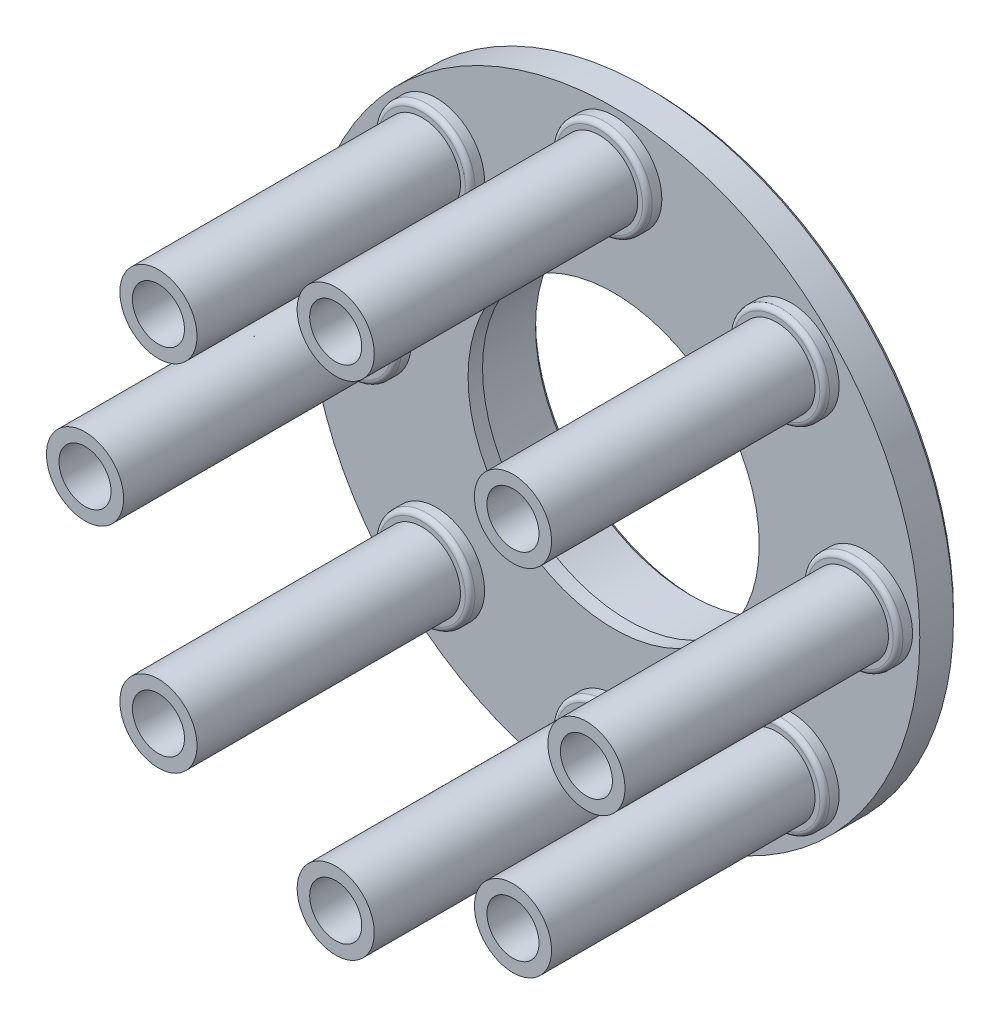
SolidWorks part; units mm, degrees
material "PLA"
ref_plane "Front Plane" through (0, 0, 0) normal (0, 0, 1) x (1, 0, 0)
ref_plane "Top Plane" through (0, 0, 0) normal (0, 1, 0) x (1, 0, 0)
ref_plane "Right Plane" through (0, 0, 0) normal (1, 0, 0) x (0, 0, -1)
sketch "Sketch1" plane through (0, 0, 0) normal (0, 0, 1) x (1, 0, 0)
  circle A0 centre (0, 0) radius 31.75
  circle A1 centre (0, 0) radius 26 construction
  circle A2 centre (0, 26) radius 2.7
  circle A3 centre (26, 0) radius 2.7
  circle A78 centre (0, -26) radius 2.7
  circle A79 centre (0, 26) radius 4.25 construction
  circle A80 centre (0, 0) radius 30.25 construction
  circle A87 centre (-26, 0) radius 2.7
  point P15 (0, 0)
  dimension "D2" = 52
  dimension "D3" = 5.4
  dimension "D5" = 8.5
  dimension "D1" = 1.5
  dimension "D4" = 4
extrude "Boss-Extrude1" add sketch "Sketch1" along normal blind 4
sketch "Sketch2" plane through (0, 0, 4) normal (0, 0, 1) x (1, 0, 0)
  circle A0 centre (0, 26) radius 4
  circle A2 centre (0, 26) radius 2.7 construction
  circle A5 centre (0, 26) radius 2.7
  point P15 (0, 0)
  dimension "D1" = 8
extrude "Boss-Extrude2" add sketch "Sketch2" along normal blind 28.8234
sketch "Sketch3" plane through (0, 0, 4) normal (0, 0, 1) x (1, 0, 0)
  arc A2 (5, 26) -> (5, 26) centre (0, 26) ccw
  circle A3 centre (0, 26) radius 5
  circle M5 centre (0, 26) radius 4
extrude "Boss-Extrude3" add sketch "Sketch3" along normal blind 1.5 contours A3 M5 region at (-4.8586, 26, 4)
sketch "Sketch4" plane through (0, 0, 4) normal (0, 0, 1) x (1, 0, 0)
  line L0 (0, 0) -> (-22.4506, 22.4506) construction
  line L1 (0, 0) -> (0, 26) construction
  circle A0 centre (0, 0) radius 31.75 construction
  circle A1 centre (0, 0) radius 31.75
  circle A2 centre (0, 26) radius 12 construction
  circle A6 centre (0, 0) radius 26 construction
  arc A8 (-13.189, 28.881) -> (-9.5294, 16.4375) centre (0, 26) ccw
  circle A9 centre (0, 0) radius 19
  circle A11 centre (0, 0) radius 14 construction
  arc A13 (-28.881, 13.189) -> (-16.4375, 9.5294) centre (-26, 0) cw
  circle A16 centre (0, 26) radius 13.5 construction
  circle A17 centre (0, 26) radius 5 construction
  point P15 (0, 0)
  point P25 (0, 0)
  dimension "D1" = 24
  dimension "D5" = 28
  dimension "D4" = 5
  dimension "D2" = 45
  dimension "D3" = 1.5
extrude "Boss-Extrude4" [suppressed] add sketch "Sketch4" along normal blind 28.8234 contours A1 A13 A9 A8
sketch "Sketch12" [suppressed] plane through (0, 0, 37.8382) normal (0, 0, 1) x (1, 0, 0)
  arc A0 (-11.2345, 15.816) -> (-15.816, 11.2345) centre (0, 0) ccw construction
  arc A1 (-11.2345, 15.816) -> (-15.816, 11.2345) centre (0, 0) ccw
  dimension "D1" = 6.4791
fillet "Fillet2" radius 0.5 1 edges at (5, 26, 5.5)
fillet "Fillet5" [suppressed] radius 1.6198
pattern_circular "CirPattern1" count 8 over 360 about axis through (0, 0, 4) along (0, 0, -1) of "Fillet2", "Boss-Extrude3", "Boss-Extrude2" reverse direction yes
ref_plane "Plane1" through (0, 0, 32.8234) normal (0, 0, 1) x (1, 0, 0)
chamfer "Chamfer1" distance 0.5 angle 45 1 edges at (31.75, 0, 0)
sketch "Sketch9" plane through (0, 0, 4) normal (0, 0, 1) x (1, 0, 0)
  circle A0 centre (0, 0) radius 8
  dimension "D1" = 16
extrude "Cut-Extrude4" cut sketch "Sketch9" against normal through all
sketch "Sketch10" plane through (0, 0, 0) normal (0, 0, -1) x (-1, 0, 0)
  circle A0 centre (0, 0) radius 8 construction
  circle A1 centre (0, 0) radius 8
  circle A2 centre (0, 0) radius 6.5
  dimension "D1" = 1.5
extrude "Boss-Extrude7" add sketch "Sketch10" against normal blind 6.5
sketch "Sketch13" plane through (0, 0, 0) normal (0, 1, 0) x (1, 0, 0)
  line L0 (0, 0) -> (0, -32.8234) construction
  line L1 (-4, -32.8234) -> (4, -32.8234) construction
  line L2 (15.6848, -4) -> (21.0848, -4) construction
  line L3 (-30, 0.5) -> (-38, -4) construction
  line L4 (-34.9404, -4) -> (-27.8293, 0)
  line L7 (31.25, 0) -> (-31.25, 0) construction
  line L8 (0, -4) -> (-38, -4) construction
  line L9 (-27.8293, 0) -> (-34.9404, 0)
  line L10 (-34.9404, 0) -> (-34.9404, -4)
  dimension "D1" = 30
  dimension "D2" = 38
  dimension "D3" = 4.5
  dimension "D4" = 1.5
sketch "Sketch14" plane through (0, 0, 4) normal (0, 0, 1) x (1, 0, 0)
  circle A0 centre (0, 0) radius 16.1
  circle A1 centre (0, 0) radius 6.5 construction
  dimension "D1" = 32.2
extrude "Cut-Extrude5" cut sketch "Sketch14" against normal through all both and the other way through all
sketch "Sketch15" plane through (0, 0, 4) normal (0, 0, 1) x (1, 0, 0)
  circle A0 centre (0, 0) radius 16.1
  circle A1 centre (0, 0) radius 15.1
  circle A2 centre (0, 0) radius 16.1 construction
  dimension "D1" = 1
extrude "Boss-Extrude8" add sketch "Sketch15" against normal blind 1.5
sketch "Sketch16" plane through (0, 0, 0) normal (0, 0, -1) x (-1, 0, 0)
  circle A0 centre (0, 0) radius 18.1
  circle A1 centre (0, 0) radius 16.1 construction
  circle M1 centre (0, 0) radius 16.1
extrude "Boss-Extrude9" add sketch "Sketch16" along normal blind 4.5 contours A0 M1 region at (17.5881, 0, 0)
chamfer "Chamfer3" distance 2 distance2 4.5 1 edges at (18.1, 0, 0) first distance on face at (18.1, 0, 0)
sketch "Sketch5" [suppressed] plane through (0, 0, 32.8234) normal (0, 0, 1) x (1, 0, 0)
  line L0 (0, 0) -> (-22.4506, 22.4506) construction
  line L1 (0, 0) -> (0, 26) construction
  circle A3 centre (-19.6222, 19.6222) radius 1.7
  circle A4 centre (0, 0) radius 31.75 construction
  arc A5 (-13.189, 28.881) -> (-28.881, 13.189) centre (0, 0) ccw construction
  dimension "D2" = 3.4
  dimension "D1" = 4
  dimension "D3" = 45
extrude "Cut-Extrude1" [suppressed] cut sketch "Sketch5" against normal through all
sketch "Sketch7" plane through (0, 0, 0) normal (0, 0, -1) x (-1, 0, 0)
  circle A0 centre (0, 26) radius 4.45
  circle A1 centre (0, 0) radius 26 construction
  point P15 (0, 0)
  dimension "D1" = 8.9
extrude "Cut-Extrude3" cut sketch "Sketch7" against normal blind 5 and the other way through all
sketch "Sketch6" [suppressed] plane through (0, 0, 0) normal (0, 0, -1) x (-1, 0, 0)
  circle A0 centre (19.6222, 19.6222) radius 2.95
  dimension "D1" = 5.9
extrude "Cut-Extrude2" [suppressed] cut sketch "Sketch6" against normal blind 3 and the other way through all
pattern_circular "CirPattern2" count 8 over 360 about axis through (0, 0, 4) along (0, 0, -1) of "Cut-Extrude3" reverse direction yes
chamfer "Chamfer4" distance 0.5 angle 45 1 edges at (-16.1, 0, -4.5)
equation "\"Nr_s\" = 132"
equation "\"module\" = 0.5"
equation "\"pressure_angle\" = 20.0"
equation "\"h_a\" = 0.5"
equation "\"h_f\" = 0.625"
equation "\"clr_tip_root\" = 0.125"
equation "\"dp_r_s\" = 66.0"
equation "\"db_r\"= \"dp_r_s\" * cos ( \"pressure_angle\" )'base CD"
equation "\"bearing_ID\" = 60"
equation "\"bearing_OD\" = 78"
equation "\"bearing_height\" = 10"
equation "\"clearance_planet\" = 1.5"
equation "\"case_dist\" = 6.5"
equation "\"Motor_case_OD_max\" = 111.3"
equation "\"case_mounting_PCD\" = 103.8"
equation "\"bearing mount thickness\" = 8"
equation "\"case_mounting_hole_dia\" = 3"
equation "\"output_mounting_PCD\" = 86"
equation "\"output_mounting_hole_dia\" = 4"
equation "\"clearance_case_mount_holes_shell_thickness\" = 1"
equation "\"motor_case_OD_base\" = 101.8"
equation "\"sec_carrier_thickness\" = 5"
equation "\"sun_coupler_hub_thickness\" = 4"
equation "\"clearance_sun_coupler_sec_carrier\" = 1.5"
equation "\"clearance_motor_and_case\" = 5"
equation "\"motor_OD\" = 86.8"
equation "\"Motor_case_thickness\" = 2.5"
equation "\"Motor_case_ID\" = 96.8"
equation "\"case_mounting_hole_shift\" = 1.0"
equation "\"output_mounting_nut_wrench_size\" = 7"
equation "\"output_mounting_nut_thickness\" = 3.2"
equation "\"case_mounting_hole_allen_socket_dia\" = 5.5"
equation "\"output_mounting_nut_depth\" = 3"
equation "\"case_mounting_bolt_depth\" = 4.5"
equation "\"Ns\" = 56"
equation "\"Np_b\" = 48"
equation "\"ring_radial_thickness\" = 5"
equation "\"ring_OD\"= \"Nr_s\" * \"module\" + \"ring_radial_thickness\" * 2"
equation "\"ring_to_chamfer_clearance\" = 1.5"
equation "\"Motor_case_OD_base_to_chamfer\" = 5"
equation "\"pattern_offset_from_motor_case_OD_base\" = 3"
equation "\"pattern_bulge_dia\" = 3"
equation "\"pattern_num_bulge\" = 18"
equation "\"pattern_depth\" = 2"
equation "\"motor_height\" = 26.5"
equation "\"case_mounting_wrench_size\" = 5.5"
equation "\"case_mounting_nut_clearance\" = 2"
equation "\"base_plate_thickness\" = 4"
equation "\"case_mounting_nut_thickness\" = 2.4"
equation "\"case_mounting_surface_height\" = 4"
equation "\"motor_mount_hole_PCD\" = 32"
equation "\"motor_mount_hole_dia\" = 4"
equation "\"motor_mount_hole_num\" = 4"
equation "\"central_hole_offset_from_motor_mount_PCD\" = 5"
equation "\"wire_slot_dist_from_center\" = 38"
equation "\"wire_slot_length\" = 10"
equation "\"wire_slot_radius\" = 2.5"
equation "\"driver_upper_holes_dist_from_center\" = 29"
equation "\"driver_lower_holes_dist_from_center\" = 13"
equation "\"driver_side_holes_dist_from_center\" = 22.5"
equation "\"driver_mount_holes_dia\" = 3"
equation "\"driver_mount_inserts_OD\" = 4.8"
equation "\"driver_mount_thickness\" = 1.5"
equation "\"driver_mount_height\" = 6"
equation "\"air_flow_hole_offset\" = 3"
equation "\"num_planet\" = 4"
equation "\"planet_pin_bolt_dia\" = 5"
equation "\"planet_pin_socket_head_dia\" = 8.5"
equation "\"carrier_PCD\" = 52.0"
equation "\"D2@Sketch1\"=\"carrier_PCD\""
equation "\"D3@Sketch1\"=\"planet_pin_bolt_dia\" + \"tight_clearance_3DP\""
equation "\"D4@Sketch1\"=\"num_planet\""
equation "\"D1@Boss-Extrude2\" = \"fw_p_s\" + \"clearance_planet\" * 2 + \"fw_p_b\""
equation "\"D1@Boss-Extrude3\"=\"clearance_planet\""
equation "\"D1@Sketch4\"=\"Np_b\"*\"module\""
equation "\"D3@Sketch4\"=\"clearance_planet\""
equation "\"D1@Boss-Extrude4\" = \"fw_p_s\" + \"clearance_planet\" * 2 + \"fw_p_b\""
equation "\"D1@Fillet2\"=\"clearance_planet\"/3"
equation "\"D1@CirPattern1\"=2*\"num_planet\""
equation "\"D1@CirPattern2\"=2*\"num_planet\""
equation "\"D1@Boss-Extrude7\"=\"bearing_height\"+ \"carrier_bearing_step_width\" - \"sun_shaft_bearing_width\""
equation "\"planet_shaft_dia\" = 8"
equation "\"D1@Sketch2\"= \"planet_shaft_dia\""
equation "\"planet_shaft_step_offset\" = 1"
equation "\"D1@Sketch3\"=\"planet_shaft_step_offset\""
equation "\"carrier_trapezoidal_support_sun_offset\" = 5"
equation "\"D4@Sketch4\"=\"carrier_trapezoidal_support_sun_offset\""
equation "\"carrier_trapezoidal_support_hole_PCD_offset_bearing_ID\" = 4"
equation "\"carrier_trapezoidal_support_hole_dia\" = 3"
equation "\"D2@Sketch5\"=\"carrier_trapezoidal_support_hole_dia\" + \"tight_clearance_3DP\""
equation "\"D1@Cut-Extrude2\"=\"carrier_trapezoidal_support_hole_dia\""
equation "\"carrier_trapezoidal_support_hole_socket_head_dia\" = 5.5"
equation "\"D1@Sketch6\"=\"carrier_trapezoidal_support_hole_socket_head_dia\" +  \"tight_clearance_3DP\""
equation "\"D1@Cut-Extrude3\"=\"planet_pin_bolt_dia\""
equation "\"D1@Sketch7\"=\"planet_pin_socket_head_dia\" + \"tight_clearance_3DP\""
equation "\"carrier_bearing_step_width\" = 1.5"
equation "\"standard_clearance_1_5mm\" = 1.5"
equation "\"standard_fillet_1_5mm\" = 1.5"
equation "\"sun_shaft_bearing_OD\" = 16"
equation "\"D1@Sketch9\"=\"sun_shaft_bearing_OD\""
equation "\"D1@Sketch10\"=\"standard_clearance_1_5mm\""
equation "\"sun_shaft_bearing_width\" = 5"
equation "\"standard_bearing_insertion_chamfer\" = 0.5"
equation "\"D1@Chamfer1\"=\"standard_bearing_insertion_chamfer\""
equation "\"D5@Sketch4\"=\"Ns\"*\"module\""
equation "\"D1@Sketch5\"=\"carrier_trapezoidal_support_hole_PCD_offset_bearing_ID\""
equation "\"D1@Plane1\" = \"fw_p_s\" + \"clearance_planet\" * 2 + \"fw_p_b\""
equation "\"D2@Sketch4\"=180/\"num_planet\""
equation "\"D3@Sketch5\"=180/\"num_planet\""
equation "\"carrier_trapezoidal_support_hole_wrench_size\" = 5.5"
equation "\"planet_pin_bolt_wrench_size\" = 8"
equation "\"pressure angle\" = 20.0"
equation "\"h_b\" = 0.625"
equation "\"dp_s\" = 28.0"
equation "\"db_s\" = 26.311393382005434"
equation "\"fw_s_calc\" = 2.7970255760332914"
equation "\"alpha_s\" = 0.8539582918412485"
equation "\"beta_s\" = 1.5063691306032174"
equation "\"dp_p_b\" = 24.0"
equation "\"db_p_b\" = 22.552622898861802"
equation "\"fw_p_s\" = 15.90536252346366"
equation "\"alpha_p_b\" = 0.8539582918412414"
equation "\"beta_p_b\" = 2.042083416317517"
equation "\"planet_bearing_OD\" = 12"
equation "\"planet_bearing_width\" = 3.5"
equation "\"planet_bore\" = 10"
equation "\"motor_output_hole_PCD\" = 23"
equation "\"motor_output_hole_dia\" = 4"
equation "\"motor_output_hole_num\" = 4"
equation "\"sun_shaft_bearing_ID\" = 8"
equation "\"sun_hub_dia\" = 30.0"
equation "\"sun_central_bolt_dia\" = 5"
equation "\"sun_central_bolt_socket_head_dia\" = 8.5"
equation "\"fw_s_used\" = 33.32338113475014"
equation "\"motor_output_hole_CSK_OD\" = 8"
equation "\"motor_output_hole_CSK_head_height\" = 2.0"
equation "\"bearing_retainer_thickness\" = 2"
equation "\"Np_s\" = 28"
equation "\"fw_p_b\" = 9.918018611286483"
equation "\"dp_p_s\" = 14.0"
equation "\"db_p_s\" = 13.155696691002717"
equation "\"alpha_p_s\" = 0.8539582918412485"
equation "\"beta_p_s\" = 4.720654844888932"
equation "\"D1@Fillet5\"= \"D1@Sketch12\" / 4"
equation "\"Nr_b\" = 152"
equation "\"dp_r_b\" = 76.0"
equation "\"db_r_b\" = 71.41663917972905"
equation "\"fw_r_b\" = 9.918018611286483"
equation "\"alpha_r_b\" = 0.8539582918412236"
equation "\"beta_r_b\" = 2.8921271099982366"
equation "\"ring_OD_b\" = 86.0"
equation "\"Fillet10\"= IIF ( \"ring_OD_b\" > ( \"bearing_OD\" + 2 * \"bearing mount thickness\" ) , \"suppressed\" , \"unsuppressed\" )"
equation "\"Fillet11\"= IIF ( \"ring_OD_b\" < ( \"bearing_OD\" + 2 * \"bearing mount thickness\" ) , \"suppressed\" , \"unsuppressed\" )"
equation "\"clr_tip_root_s\" = 0.125"
equation "\"db_r_s\" = 62.01971297186996"
equation "\"fw_r_s\" = 14.40536252346366"
equation "\"alpha_r_s\" = 0.8539582918412449"
equation "\"beta_r_s\" = 3.071552947318853"
equation "\"D1@Sketch13\"=\"bearing_ID\"/2"
equation "\"D2@Sketch13\"=(\"Nr_s\"*\"module\"+\"ring_radial_thickness\"*2)*0.5"
equation "\"D3@Sketch13\"=\"standard_clearance_1_5mm\"*3"
equation "\"D4@Sketch13\"=\"standard_clearance_1_5mm\""
equation "\"D5@Sketch1\"=\"planet_pin_socket_head_dia\""
equation "\"D1@Sketch1\"=\"standard_clearance_1_5mm\""
equation "\"small_ring_case_thickness\" = 4"
equation "\"carrier_thickness\" = 4"
equation "\"small_ring_output_wall_thickness\" = 5"
equation "\"small_ring_output_wall_to_bearing_shaft_attachement_hole_dia\" = 4"
equation "\"small_ring_output_wall_to_bearing_shaft_attachement_hole_depth\" = 6.5"
equation "\"small_ring_output_wall_to_bearing_shaft_attachement_nut_wrench\" = 7"
equation "\"small_ring_output_wall_to_bearing_shaft_attachement_nut_thickness\" = 3.2"
equation "\"small_ring_output_wall_to_bearing_shaft_attachement_hole_pcd\" = 12"
equation "\"small_ring_output_wall_to_bearing_shaft_attachement_hole_num\" = 3"
equation "\"small_ring_output_wall_to_bearing_shaft_attachement_hole_CSK_OD\" = 8"
equation "\"small_ring_output_wall_to_bearing_shaft_attachement_hole_CSK_head_height\" = 2.0"
equation "\"carrier_small_ring_inner_bearing_ID\" = 20"
equation "\"carrier_small_ring_inner_bearing_OD\" = 32"
equation "\"carrier_small_ring_inner_bearing_height\" = 7"
equation "\"carrier_small_ring_inner_bearing_flap\" = 2"
equation "\"gear_casing_big_ring_to_bearing_dist\" = 24.90536252346366"
equation "\"gear_casing_thickness\" = 4"
equation "\"D1@Boss-Extrude1\"=\"carrier_thickness\""
equation "\"D1@Boss-Extrude9\"= \"carrier_small_ring_inner_bearing_height\" - \"carrier_thickness\" + \"standard_clearance_1_5mm\""
equation "\"D3@Chamfer3\"=\"carrier_small_ring_inner_bearing_height\"-\"carrier_thickness\" + \"standard_clearance_1_5mm\""
equation "\"D1@Chamfer3\"=\"standard_clearance_1_5mm\"*4/3"
equation "\"D1@Sketch14\"=\"carrier_small_ring_inner_bearing_OD\" + \"tight_clearance_3DP\"/2"
equation "\"D1@Sketch16\"=\"standard_clearance_1_5mm\"*4/3"
equation "\"tight_clearance_3DP\"= 0.4"
equation "\"loose_clearance_3DP\"= 0.8"
equation "\"D1@Chamfer4\"= \"standard_bearing_insertion_chamfer\""
